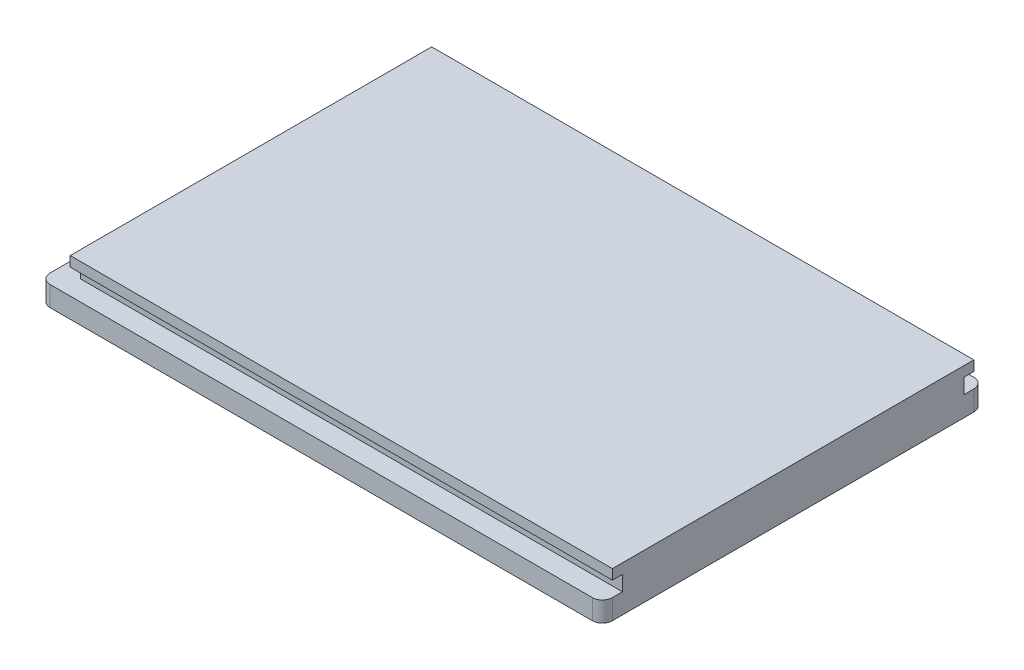
SolidWorks part; units mm, degrees
ref_plane "Front Plane" through (0, 0, 0) normal (0, 0, 1) x (1, 0, 0)
ref_plane "Top Plane" through (0, 0, 0) normal (0, 1, 0) x (1, 0, 0)
ref_plane "Right Plane" through (0, 0, 0) normal (1, 0, 0) x (0, 0, -1)
sketch "Sketch1" plane through (0, 0, 0) normal (0, 1, 0) x (1, 0, 0)
  line L1 (0, 0) -> (140, 0)
  line L2 (0, 0) -> (0, 95)
  line L3 (0, 95) -> (140, 95)
  line L4 (140, 0) -> (140, 95)
  dimension "D1" = 95
  dimension "D2" = 140
extrude "Boss-Extrude1" add sketch "Sketch1" along normal blind 5
sketch "Sketch2" plane through (0, 5, 0) normal (0, 1, 0) x (1, 0, 0)
  line L0 (0, 95) -> (0, 90) construction
  line L1 (0, 95) -> (0, 0) construction
  line L2 (0, 90) -> (5, 90) construction
  line L3 (5, 90) -> (140, 90)
  line L5 (140, 0) -> (140, 95) construction
  line L6 (140, 90) -> (140, 5)
  line L7 (140, 5) -> (5, 5)
  line L8 (5, 90) -> (5, 5)
  dimension "D1" = 5
extrude "Boss-Extrude2" add sketch "Sketch2" along normal blind 3.75
sketch "Sketch3" plane through (0, 8.75, 0) normal (0, 1, 0) x (1, 0, 0)
  line L0 (5, 90) -> (5, 92.5) construction
  line L1 (5, 5) -> (5, 2.5) construction
  line L2 (5, 2.5) -> (5, 92.5)
  line L4 (5, 2.5) -> (140, 2.5)
  line L6 (5, 92.5) -> (140, 92.5)
  line L7 (140, 2.5) -> (140, 92.5)
  line L8 (140, 5) -> (140, 90) construction
  dimension "D1" = 2.5
extrude "Boss-Extrude3" add sketch "Sketch3" along normal blind 2.5
fillet "Fillet2" radius 2.5 4 edges at (140, 2.5, 0) (140, 2.5, -95) (0, 2.5, 0) (0, 2.5, -95)
